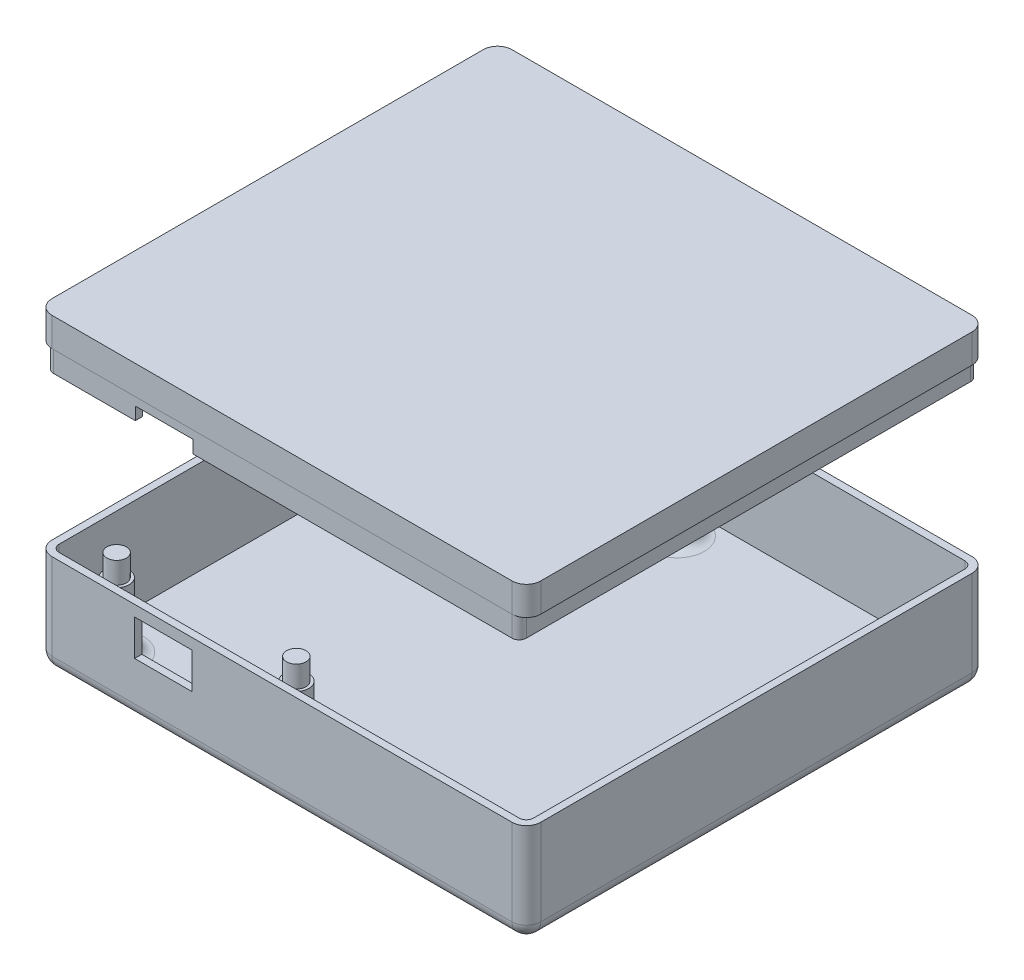
SolidWorks part; units mm, degrees
note: The reader was unsure of these and kept them because the rebuilt part matched: shared geometry of "Sketch1<2>".
ref_plane "Front Plane" through (0, 0, 0) normal (0, 0, 1) x (1, 0, 0)
ref_plane "Top Plane" through (0, 0, 0) normal (0, 1, 0) x (1, 0, 0)
ref_plane "Right Plane" through (0, 0, 0) normal (1, 0, 0) x (0, 0, -1)
sketch "Sketch1" plane through (0, 0, 0) normal (0, 1, 0) x (1, 0, 0)
  line L1 (33, -31) -> (-33, -31)
  line L2 (33, -31) -> (33, 31)
  line L3 (33, 31) -> (-33, 31)
  line L4 (-33, -31) -> (-33, 31)
  line L5 (33, -31) -> (-33, 31) construction
  line L6 (33, 31) -> (-33, -31) construction
  point P1 (0, 0)
  dimension "D1" = 66
  dimension "D2" = 62
extrude "Extrude-Thin1" add sketch "Sketch1" along normal blind 14 thin thin type one direction wall 1
extrude "Boss-Extrude1" add sketch "Sketch1<2>" along normal blind 1
sketch "Sketch1<2>" plane through (0, 0, 0) normal (0, 1, 0) x (1, 0, 0) same geometry as "Sketch1"
sketch "Sketch3" plane through (0, 1, 0) normal (0, 1, 0) x (1, 0, 0)
  line L0 (-33, 31) -> (-33, -31) construction
  line L1 (33, 31) -> (-33, 31) construction
  circle A0 centre (-29, 27) radius 1.75
  dimension "D1" = 3.5
  dimension "D2" = 4
  dimension "D3" = 4
extrude "Boss-Extrude2" add sketch "Sketch3" along normal blind 9
sketch "Sketch5" plane through (0, 1, 0) normal (0, 1, 0) x (1, 0, 0)
  line L0 (-33, 31) -> (-33, -31) construction
  circle A0 centre (-29, -26) radius 1.75
  circle A1 centre (-29, 27) radius 1.75 construction
  dimension "D1" = 3.5
  dimension "D2" = 53
  dimension "D3" = 4
extrude "Boss-Extrude3" add sketch "Sketch5" along normal blind 9
sketch "Sketch7" plane through (0, 10, 0) normal (0, 1, 0) x (1, 0, 0)
  circle A0 centre (-29, 27) radius 1.35
  dimension "D1" = 2.7
extrude "Boss-Extrude4" add sketch "Sketch7" along normal blind 3
sketch "Sketch8" plane through (0, 10, 0) normal (0, 1, 0) x (1, 0, 0)
  circle A0 centre (-29, -26) radius 1.35
  dimension "D1" = 2.7
extrude "Boss-Extrude5" add sketch "Sketch8" along normal blind 3
fillet "Fillet2" radius 2 8 edges at (34, 0, 0) (-34, 0, 0) (0, 0, -32) (0, 0, 32) (-34, 7, 32) (34, 7, 32) (34, 7, -32) (-34, 7, -32)
fillet "Fillet3" radius 2 1 edges at (-29, 1, -25.25)
fillet "Fillet4" radius 2 1 edges at (-29, 1, 27.75)
sketch "Sketch10" plane through (0, 1, 0) normal (0, 1, 0) x (1, 0, 0)
  line L0 (-33, 0) -> (-16.5, 0) construction
  line L4 (-33, 31) -> (-33, -31) construction
  line L5 (-16.5, -31) -> (-16.5, 31)
  line L6 (33, 31) -> (-33, 31) construction
  point P11 (-16.5, 0)
  dimension "D1" = 16.5
ref_plane "Plane2" through (-16.5, 0, 0) normal (1, 0, 0) x (0, 0, -1)
mirror "Mirror1" about plane through (-16.5, 0, 0) normal (1, 0, 0) of "Fillet4", "Fillet3", "Boss-Extrude2", "Boss-Extrude3", "Boss-Extrude4", "Boss-Extrude5"
sketch "Sketch12" plane through (0, 1, 0) normal (0, 1, 0) x (1, 0, 0)
  line L0 (-4, -26) -> (-29, -26) construction
sketch "Sketch14" plane through (0, 0, -31) normal (0, 0, 1) x (1, 0, 0)
  line L1 (-12.5, 12.481) -> (-20.5, 12.481)
  line L2 (-12.5, 12.481) -> (-12.5, 7.481)
  line L3 (-12.5, 7.481) -> (-20.5, 7.481)
  line L4 (-20.5, 12.481) -> (-20.5, 7.481)
  line L5 (-12.5, 12.481) -> (-20.5, 7.481) construction
  line L6 (-12.5, 7.481) -> (-20.5, 12.481) construction
  point P0 (-16.5, 9.981)
  dimension "D1" = 5
  dimension "D2" = 8
  dimension "D3" = 8.981
extrude "Cut-Extrude1" cut sketch "Sketch14" along normal blind 126.5 from offset 2
fillet "Fillet7" radius 1 4 edges at (33, 7.5, -31) (-33, 7.5, -31) (-33, 7.5, 31) (33, 7.5, 31)
sketch "Sketch22" plane through (0, 1, 0) normal (0, 1, 0) x (1, 0, 0)
  line L4 (-34, 30) -> (-34, -30)
  line L5 (-32, -32) -> (32, -32)
  line L6 (34, -30) -> (34, 30)
  line L7 (32, 32) -> (-32, 32)
  line L8 (-34, 30) -> (-34, -30)
  line L9 (-32, -32) -> (32, -32)
  line L10 (34, -30) -> (34, 30)
  line L11 (32, 32) -> (-32, 32)
  arc A4 (-34, -30) -> (-32, -32) centre (-32, -30) ccw
  arc A5 (32, -32) -> (34, -30) centre (32, -30) ccw
  arc A6 (34, 30) -> (32, 32) centre (32, 30) ccw
  arc A7 (-32, 32) -> (-34, 30) centre (-32, 30) ccw
  arc A8 (-34, -30) -> (-32, -32) centre (-32, -30) ccw
  arc A9 (32, -32) -> (34, -30) centre (32, -30) ccw
  arc A10 (34, 30) -> (32, 32) centre (32, 30) ccw
  arc A11 (-32, 32) -> (-34, 30) centre (-32, 30) ccw
  dimension "D1" = 0
extrude "Boss-Extrude9" add sketch "Sketch22" along normal blind 4 and the other way blind 0.01 from offset 20 separate body
shell "Shell1" thickness 1 removed face at (0, 20.99, 0)
sketch "Sketch25" plane through (0, 25, 0) normal (0, 1, 0) x (1, 0, 0)
  line L1 (32.9, 31.9) -> (-32.9, 31.9)
  line L2 (32.9, 31.9) -> (32.9, -31.9)
  line L3 (32.9, -31.9) -> (-32.9, -31.9)
  line L4 (-32.9, 31.9) -> (-32.9, -31.9)
  line L5 (32.9, 31.9) -> (-32.9, -31.9) construction
  line L6 (32.9, -31.9) -> (-32.9, 31.9) construction
  point P0 (0, 0)
  dimension "D1" = 65.8
  dimension "D2" = 63.8
extrude "Extrude-Thin5" add sketch "Sketch25" against normal blind 7 thin thin type one direction reverse wall 1
fillet "Fillet8" radius 1 4 edges at (32.9, 21.5, 31.9) (-32.9, 21.5, 31.9) (-32.9, 21.5, -31.9) (32.9, 21.5, -31.9)
move or copy body "Body-Move/Copy7" bodies to move or copy 133 copy no translate (0, 18.0762, 0) parameters "D1"=0, "D2"=18.0762, "D3"=0
sketch "Sketch26" plane through (0, 0, 31.9) normal (0, 0, 1) x (1, 0, 0)
  line L0 (-12.5, 12.481) -> (-12.5, 36.0762) construction
  line L1 (-31.9, 36.0762) -> (31.9, 36.0762) construction
  line L2 (-20.5, 12.481) -> (-20.5, 36.0762) construction
  line L4 (-12.5, 36.0762) -> (-20.5, 36.0762)
  line L5 (-12.5, 36.0762) -> (-12.5, 37.841)
  line L6 (-12.5, 37.841) -> (-20.5, 37.841)
  line L7 (-20.5, 36.0762) -> (-20.5, 37.841)
extrude "Cut-Extrude2" cut sketch "Sketch26" against normal blind 10
ref_plane "Plane3" through (0, 20, 0) normal (0, 1, 0) x (1, 0, 0)
split "Split1" trim tools "Plane3" bodies to split 108 136 resulting bodies 137 138
